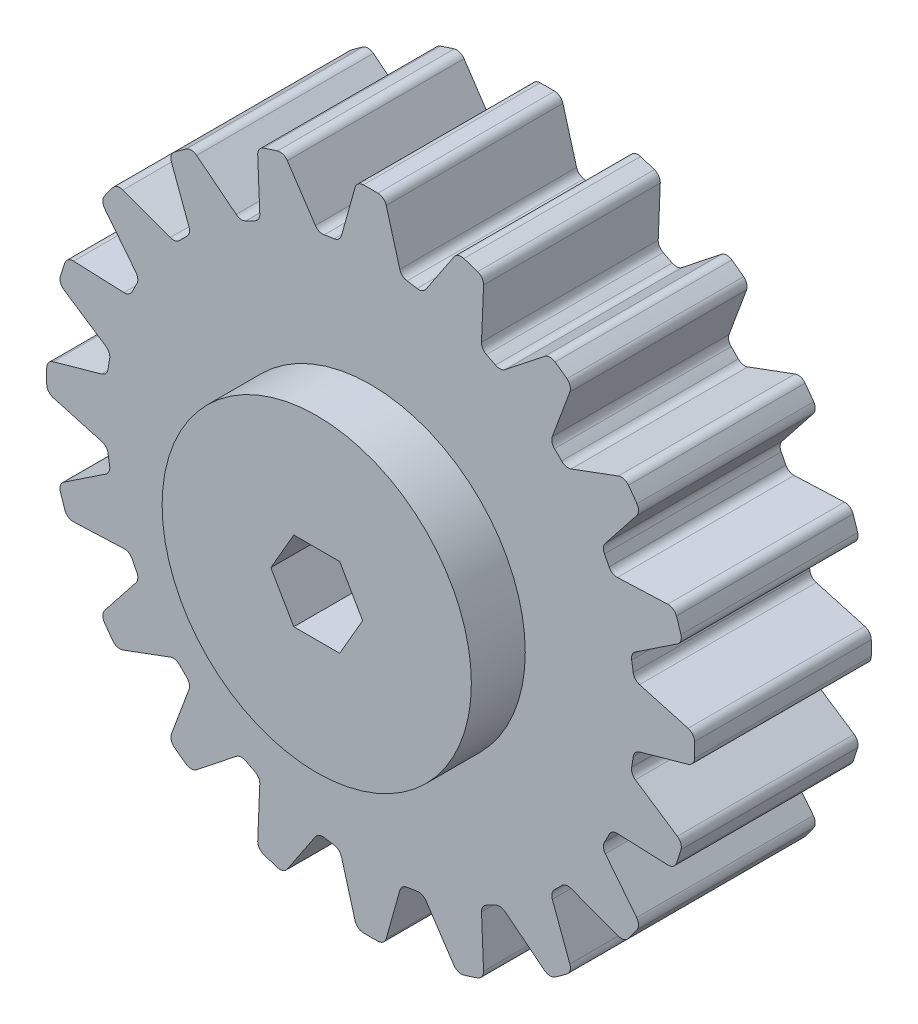
SolidWorks part; units mm, degrees
ref_plane "Front Plane" through (0, 0, 0) normal (0, 0, 1) x (1, 0, 0)
ref_plane "Top Plane" through (0, 0, 0) normal (0, 1, 0) x (1, 0, 0)
ref_plane "Right Plane" through (0, 0, 0) normal (1, 0, 0) x (0, 0, -1)
sketch "Sketch1" plane through (0, 0, 0) normal (0, 0, 1) x (1, 0, 0)
  circle A2 centre (0, 0) radius 9
  dimension "Blank diameter" = 18
extrude "Body" add sketch "Sketch1" against normal blind 6
sketch "Sketch2" plane through (0, 0, 0) normal (0, 0, 1) x (1, 0, 0)
  line L0 (0, 16.3446) -> (0, 3.6554) construction
  line L1 (-0.755, 9.9715) -> (-1.0446, 8.9392)
  line L2 (-0.755, 9.9715) -> (-0.4693, 10.99)
  line L3 (0.755, 9.9715) -> (1.0446, 8.9392)
  line L4 (0.755, 9.9715) -> (0.4693, 10.99)
  line L5 (0, 0) -> (-3.338, 44.0862) construction
  line L6 (0, 0) -> (3.224, 42.5807) construction
  arc A0 (0.4693, 10.99) -> (-0.4693, 10.99) centre (0, 0) ccw
  arc A1 (0.755, 9.9715) -> (-0.755, 9.9715) centre (0, 0) ccw construction
  arc A2 (1.0446, 8.9392) -> (-1.0446, 8.9392) centre (0, 0) ccw
  point P1 (0, 10)
  dimension "D2" = 20
  dimension "D3" = 20
  dimension "Full diameter" = 22
  dimension "Pitch diameter" = 20
  dimension "Blank diameter" = 18
  dimension "Tooth width PCD" = 1.51
extrude "Tooth" add sketch "Sketch2" against normal blind 6
fillet "Tooth Fillet" radius 0.3 4 edges at (-0.4693, 10.99, -3) (-1.0446, 8.9392, -3) (0.4693, 10.99, -3) (1.0446, 8.9392, -3)
pattern_circular "Tooth Pattern" count 20 over 360 about axis through (0, 0, 0) along (0, 0, 1) of "Tooth", "Tooth Fillet"
ref_axis "Axis1" through (0, 0, 0) along (0, 0, -1)
sketch "Sketch3" plane through (0, 0, 0) normal (0, 0, 1) x (1, 0, 0)
  circle A0 centre (0, 0) radius 5.25
  circle A1 centre (0, 0) radius 8
  dimension "Plastic boss" = 10.5
  dimension "Resses" = 16
extrude "Resses1" [suppressed] cut sketch "Sketch3" against normal blind 1
sketch "Sketch4" plane through (0, 0, -6) normal (0, 0, -1) x (-1, 0, 0)
  circle A0 centre (0, 0) radius 8
  circle A1 centre (0, 0) radius 5.25
  dimension "Plastic boss" = 10.5
  dimension "Resses" = 16
extrude "Resses2" cut sketch "Sketch4" against normal blind 1
sketch "Sketch5" plane through (0, 0, -6) normal (0, 0, -1) x (-1, 0, 0)
  circle A0 centre (0, 0) radius 5
  dimension "D1" = 10
extrude "Brass boss" [suppressed] add sketch "Sketch5" along normal blind 5.7
sketch "Sketch6" [suppressed] plane through (0, 0, -11.7) normal (0, 0, -1) x (-1, 0, 0)
  circle A0 centre (0, 0) radius 2
  dimension "D1" = 4
extrude "Bore" [suppressed] cut sketch "Sketch6" against normal through all
sketch "Sketch7" plane through (0, 0, 0) normal (0, 1, 0) x (1, 0, 0)
  circle A0 centre (0, 8.8626) radius 1
  dimension "D1" = 2
extrude "Grub screw" [suppressed] cut sketch "Sketch7" against normal through all
sketch "Sketch8" plane through (0, 0, -5) normal (0, 0, -1) x (-1, 0, 0)
  circle A0 centre (-0.8321, 10.5608) radius 1.8434
extrude "Extrude1" [suppressed] add sketch "Sketch8" along normal blind 5
sketch "Sketch9" plane through (0, 0, -6) normal (0, 0, -1) x (-1, 0, 0)
  circle A0 centre (0, 0) radius 5.25 construction
  circle A1 centre (0, 0) radius 5.25
extrude "Boss-Extrude1" add sketch "Sketch9" along normal blind 1.83 and the other way blind 7.83
sketch "Sketch10" plane through (0, 0, -7.83) normal (0, 0, -1) x (-1, 0, 0)
  line L1 (0.7794, 1.35) -> (-0.7794, 1.35)
  line L2 (-0.7794, 1.35) -> (-1.5588, 0)
  line L3 (-1.5588, 0) -> (-0.7794, -1.35)
  line L4 (-0.7794, -1.35) -> (0.7794, -1.35)
  line L5 (0.7794, -1.35) -> (1.5588, 0)
  line L6 (1.5588, 0) -> (0.7794, 1.35)
  circle A0 centre (0, 0) radius 1.35 construction
  dimension "D1" = 2.7
extrude "Cut-Extrude1" cut sketch "Sketch10" against normal through all
sketch "Sketch11" plane through (0, 0, -5) normal (0, 0, -1) x (-1, 0, 0)
  circle A0 centre (0, 0) radius 5.25 construction
  circle A1 centre (0, 0) radius 8
  circle A2 centre (0, 0) radius 8
  circle A3 centre (0, 0) radius 5.25
  dimension "D1" = 0
extrude "Boss-Extrude2" add sketch "Sketch11" along normal up to surface (1 mm away) up to face at (-8, 0, -6)
